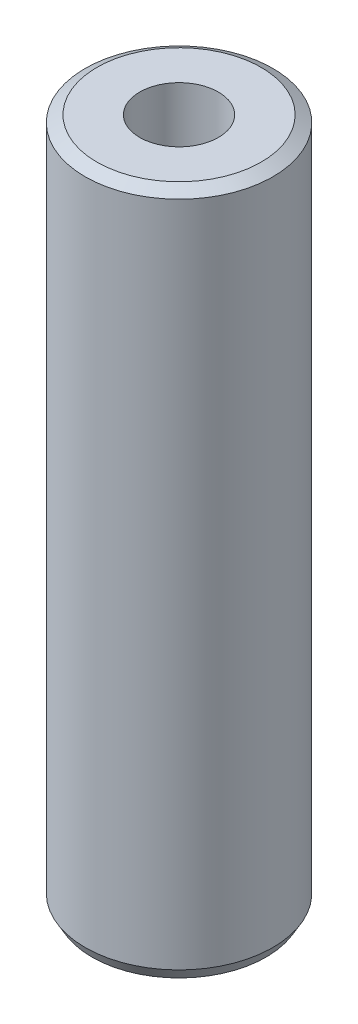
SolidWorks part; units mm, degrees
ref_plane "Front Plane" through (0, 0, 0) normal (0, 0, 1) x (1, 0, 0)
ref_plane "Top Plane" through (0, 0, 0) normal (0, 1, 0) x (1, 0, 0)
ref_plane "Right Plane" through (0, 0, 0) normal (1, 0, 0) x (0, 0, -1)
sketch "Sketch1" plane through (0, 0, 0) normal (0, 1, 0) x (1, 0, 0)
  circle A0 centre (0, 0) radius 55
  dimension "SHAFT_OD" = 110
extrude "Boss-Extrude1" add sketch "Sketch1" along normal blind 401.9233
sketch "Sketch2" plane through (0, 0, 0) normal (0, 1, 0) x (1, 0, 0)
  circle A0 centre (0, 0) radius 23.0586
  dimension "BORE_D" = 46.1171
extrude "Cut-Extrude1" cut sketch "Sketch2" along normal through all
chamfer "Chamfer1" distance 3.9792 angle 60 2 edges at (0, 401.9233, 55) (0, 0, 55) first distance on face at (0, 401.9233, 55) first distance on face at (0, 0, 23.0586)
